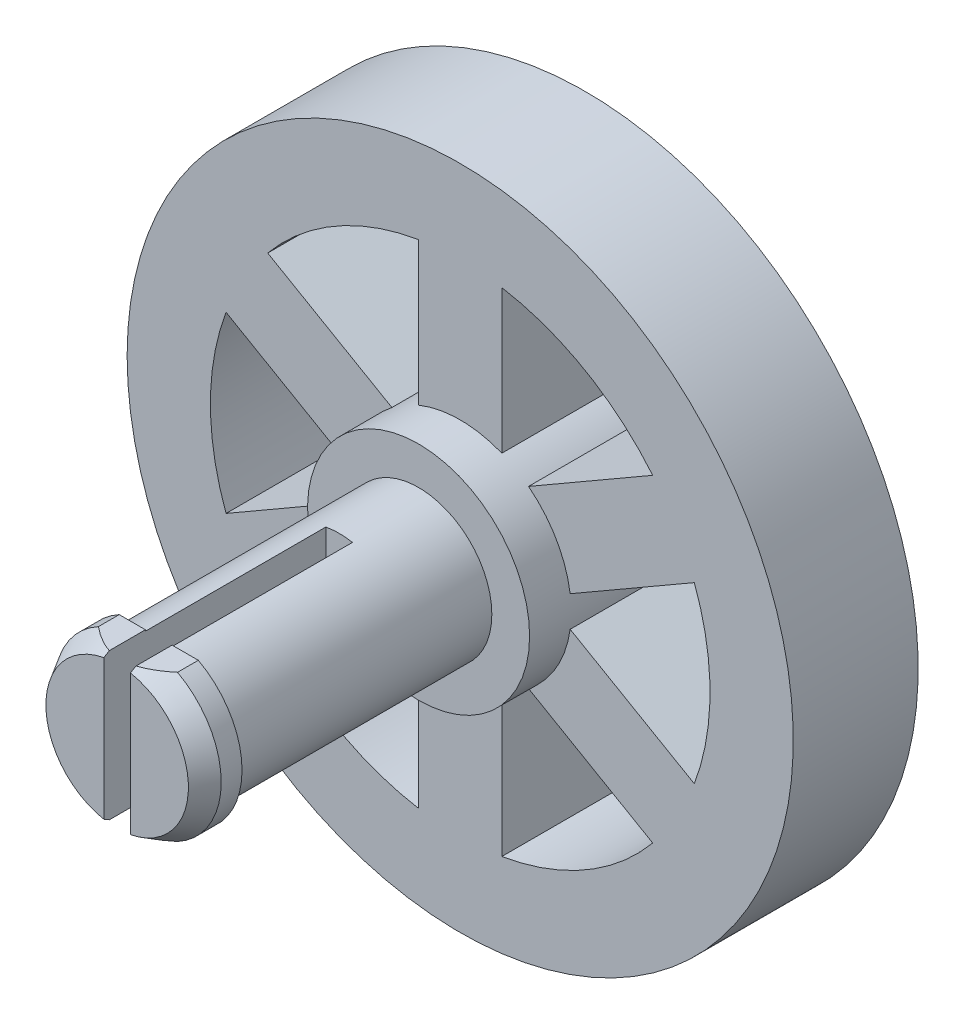
SolidWorks part; units mm, degrees
ref_plane "Front Plane" through (0, 0, 0) normal (0, 0, 1) x (1, 0, 0)
ref_plane "Top Plane" through (0, 0, 0) normal (0, 1, 0) x (1, 0, 0)
ref_plane "Right Plane" through (0, 0, 0) normal (1, 0, 0) x (0, 0, -1)
sketch "Sketch1" plane through (0, 0, 0) normal (0, 0, 1) x (1, 0, 0)
  line L0 (-1.5875, 3.9244) -> (-1.5875, 9.3918)
  line L1 (1.5875, 3.9244) -> (1.5875, 9.3918)
  line L2 (2.6049, 3.337) -> (7.3398, 6.0707)
  line L3 (4.1924, 0.5874) -> (8.9273, 3.3211)
  line L4 (4.1924, -0.5874) -> (8.9273, -3.3211)
  line L5 (2.6049, -3.337) -> (7.3398, -6.0707)
  line L6 (1.5875, -3.9244) -> (1.5875, -9.3918)
  line L7 (-1.5875, -3.9244) -> (-1.5875, -9.3918)
  line L8 (-2.6049, -3.337) -> (-7.3398, -6.0707)
  line L9 (-4.1924, -0.5874) -> (-8.9273, -3.3211)
  line L10 (-4.1924, 0.5874) -> (-8.9273, 3.3211)
  line L11 (-2.6049, 3.337) -> (-7.3398, 6.0707)
  circle A0 centre (0, 0) radius 12.7
  circle A1 centre (0, 0) radius 9.525
  circle A2 centre (0, 0) radius 4.2333
  point P32 (0, 0)
  dimension "D1" = 25.4
  dimension "D2" = 3.175
  dimension "D3" = 8.4667
  dimension "D4" = 3.175
  dimension "D5" = 6
extrude "Boss-Extrude1" add sketch "Sketch1" along normal blind 6.35 contours A2 region at (0, 0, 0)
extrude "Boss-Extrude2" add sketch "Sketch1<3>" along normal blind 4.7625 contours A2 L3 A1 L2 | A2 L5 A1 L4 | A2 L7 A1 L6 | A2 L9 A1 L8 | A2 L11 A1 L10 | A2 L1 A1 L0 region at (0, 6.8057, 0) region at (-5.8939, 3.4028, 0) region at (5.8939, 3.4028, 0) region at (-5.8939, -3.4028, 0) region at (5.8939, -3.4028, 0) region at (0, -6.8057, 0)
sketch "Sketch1<3>" plane through (0, 0, 0) normal (0, 0, 1) x (1, 0, 0) same geometry as "Sketch1"
extrude "Boss-Extrude3" add sketch "Sketch1<4>" along normal blind 4.7625 contours A0 A1 region at (-12.3408, 0, 0)
sketch "Sketch1<4>" plane through (0, 0, 0) normal (0, 0, 1) x (1, 0, 0) same geometry as "Sketch1"
sketch "Sketch2" plane through (0, 0, 6.35) normal (0, 0, 1) x (1, 0, 0)
  circle A0 centre (0, 0) radius 2.794
  dimension "D1" = 5.588
extrude "Boss-Extrude4" add sketch "Sketch2" along normal blind 9.906
sketch "Sketch3" plane through (0, 0, 16.256) normal (0, 0, 1) x (1, 0, 0)
  circle A0 centre (0, 0) radius 3.175
  dimension "D1" = 6.35
extrude "Boss-Extrude5" add sketch "Sketch3" along normal blind 1.5875
sketch "Sketch4" plane through (0, 0, 0) normal (1, 0, 0) x (0, 0, -1)
  line L1 (-17.8435, 3.175) -> (-9.3768, 3.175)
  line L2 (-17.8435, 3.175) -> (-17.8435, -3.175)
  line L3 (-17.8435, -3.175) -> (-9.3768, -3.175)
  line L4 (-9.3768, 3.175) -> (-9.3768, -3.175)
  dimension "D1" = 8.4667
extrude "Cut-Extrude1" cut sketch "Sketch4" against normal mid plane 1.016
sketch "Sketch5" plane through (0, 0, 17.8435) normal (0, 0, 1) x (1, 0, 0)
  line L1 (-3.175, 4.2333) -> (3.175, 4.2333)
  line L2 (-3.175, 4.2333) -> (-3.175, 2.794)
  line L3 (-3.175, 2.794) -> (3.175, 2.794)
  line L4 (3.175, 4.2333) -> (3.175, 2.794)
  line L5 (-4.2333, -4.2333) -> (4.2333, -4.2333)
  line L6 (-4.2333, -4.2333) -> (-4.2333, -2.794)
  line L7 (-4.2333, -2.794) -> (4.2333, -2.794)
  line L8 (4.2333, -4.2333) -> (4.2333, -2.794)
  arc A0 (0.508, 2.7474) -> (-0.508, 2.7474) centre (0, 0) ccw construction
  arc A1 (0.508, -3.1341) -> (0.508, 3.1341) centre (0, 0) ccw construction
  arc A2 (-0.508, 3.1341) -> (-0.508, -3.1341) centre (0, 0) ccw construction
  circle A3 centre (0, 0) radius 4.2333 construction
  arc A4 (-0.508, -2.7474) -> (0.508, -2.7474) centre (0, 0) ccw construction
  arc A5 (-1.5875, -3.9244) -> (1.5875, -3.9244) centre (0, 0) ccw construction
extrude "Cut-Extrude2" cut sketch "Sketch5" against normal blind 1.5875
chamfer "Chamfer1" distance 0.7937 angle 30 1 edges at (-3.175, 0, 17.8435) first distance on face at (-2.3415, 0, 17.0497)
chamfer "Chamfer2" distance 0.7937 angle 30 1 edges at (3.175, 0, 17.8435) first distance on face at (2.3415, 0, 17.0497)
